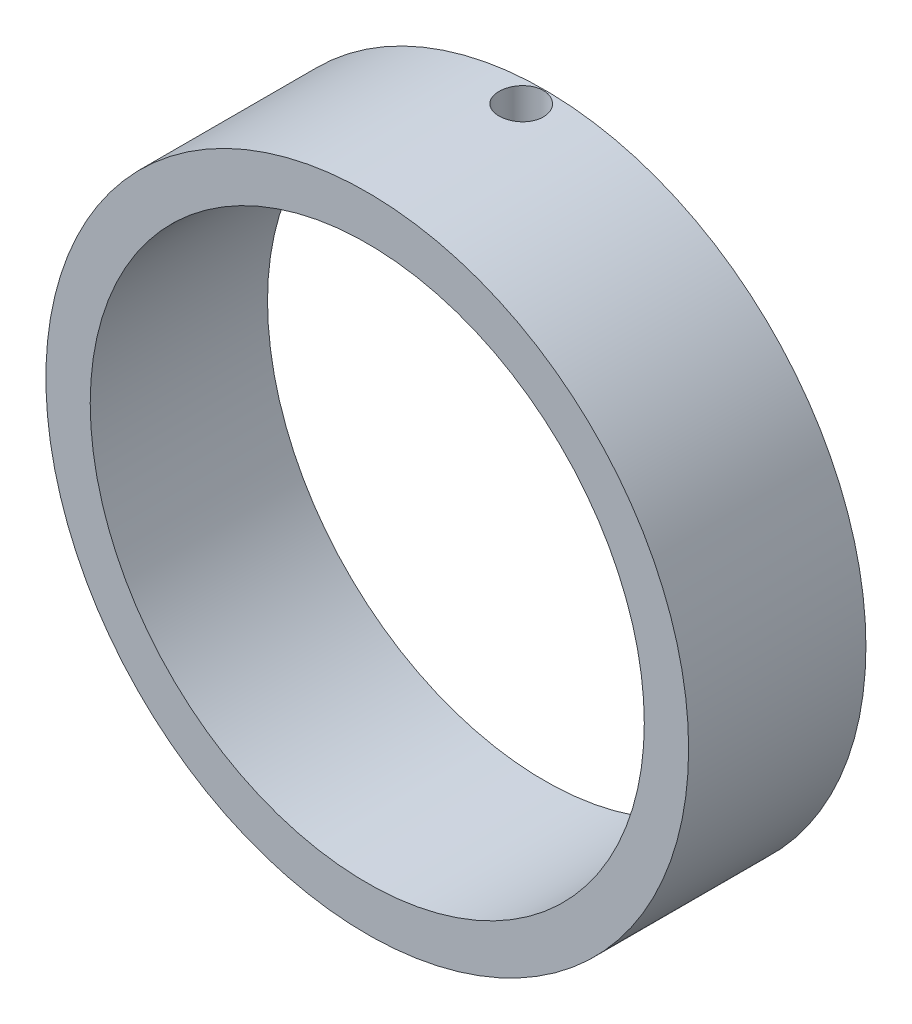
SolidWorks part; units mm, degrees
material "Alumina"
ref_plane "Front Plane" through (0, 0, 0) normal (0, 0, 1) x (1, 0, 0)
ref_plane "Top Plane" through (0, 0, 0) normal (0, 1, 0) x (1, 0, 0)
ref_plane "Right Plane" through (0, 0, 0) normal (1, 0, 0) x (0, 0, -1)
sketch "Sketch1" plane through (0, 0, 0) normal (0, 0, 1) x (1, 0, 0)
  circle A0 centre (0, 0) radius 29
  circle A1 centre (0, 0) radius 25
  dimension "D1" = 58
  dimension "D2" = 50
extrude "Boss-Extrude1" add sketch "Sketch1" along normal blind 16
ref_plane "Plane1" through (0, 29, 0) normal (0, 1, 0) x (1, 0, 0)
ref_plane "Plane2" through (0, -29, 0) normal (0, 1, 0) x (1, 0, 0)
sketch "Sketch3" plane through (0, 29, 0) normal (0, 1, 0) x (1, 0, 0)
  line L0 (0, 0) -> (0, -19.4683) construction
  line L1 (0, -19.4683) -> (0, 6.7745) construction
  circle A0 centre (0, -2.1089) radius 2
  dimension "D1" = 4
extrude "Cut-Extrude1" cut sketch "Sketch3" against normal blind 16
